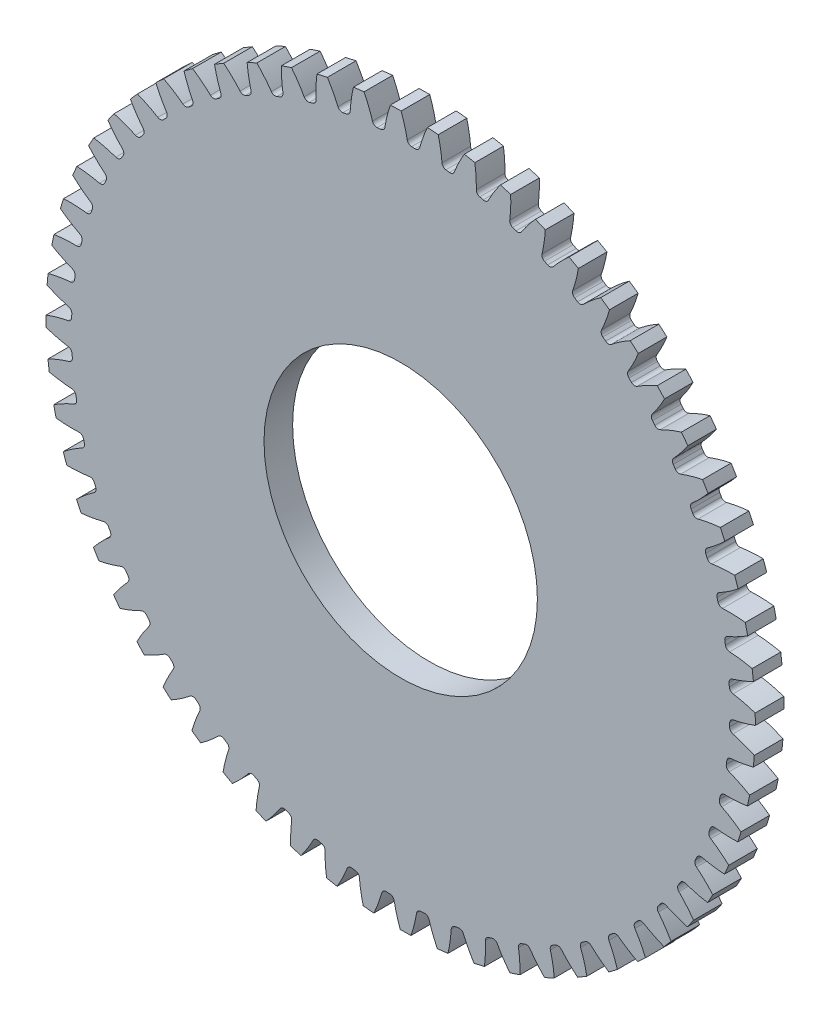
SolidWorks part; units mm, degrees
ref_plane "Front" through (0, 0, 0) normal (0, 0, 1) x (1, 0, 0)
ref_plane "Top" through (0, 0, 0) normal (0, 1, 0) x (1, 0, 0)
ref_plane "Right" through (0, 0, 0) normal (1, 0, 0) x (0, 0, -1)
sketch "Sketch3" plane through (0, 0, 0) normal (0, 0, 1) x (1, 0, 0)
  circle A0 centre (0, 0) radius 78.74
  dimension "od" = 157.48
extrude "gearBody" add sketch "Sketch3" along normal blind 6.35
sketch "Sketch2" plane through (0, 0, 0) normal (0, 0, 1) x (1, 0, 0)
  line L0 (0, 0) -> (68.1572, 28.2316) construction
  line L1 (92.002, -18.3096) -> (0, 0) construction
  line L2 (0, 0) -> (36.3143, 0) construction
  line L3 (76.1945, -0.916) -> (76.0401, -4.9343) construction
  line L5 (76.1173, -2.9252) -> (0, 0) construction
  line L7 (0, 0) -> (73.7729, 0) construction
  arc A0 (73.758, -1.4806) -> (73.6541, -4.1844) centre (0, 0) ccw construction
  arc A1 (78.7399, -0.0913) -> (78.5147, -5.9519) centre (0, 0) ccw construction
  arc A2 (76.1945, -0.916) -> (76.0401, -4.9343) centre (0, 0) ccw construction
  arc A3 (73.031, -3.2028) -> (73.0614, -2.4115) centre (0, 0) ccw
  arc A4 (92.002, -18.3096) -> (73.7695, -4.2158) centre (65.7895, -33.3792) ccw
  arc A5 (92.002, -18.3096) -> (93.1358, 11.1948) centre (0, 0) ccw
  arc A6 (93.1358, 11.1948) -> (73.8754, -1.4582) centre (68.1572, 28.2316) cw
  arc A7 (73.0614, -2.4115) -> (73.8754, -1.4582) centre (74.0654, -2.4446) cw
  arc A8 (73.7695, -4.2158) -> (73.031, -3.2028) centre (74.0346, -3.2468) cw
  point P6 (93.1358, 11.1948)
  point P22 (92.002, -18.3096)
  dimension "baseDia" = 147.5457
  dimension "od" = 157.48
  dimension "pd" = 152.4
  dimension "rd" = 146.2024
  dimension "rFillet" = 1.0046
  dimension "pointX" = 93.1358
  dimension "pointY" = 11.1948
  dimension "CTT" = 4.0183
  dimension "flankCenterAngle" = 22.5
extrude "toothCut" cut sketch "Sketch2" along normal through all
pattern_circular "CirPattern1" count 60 over 360 about axis through (0, 0, 6.35) along (0, 0, -1) of "toothCut"
ref_axis "toothSpace" through (0, 0, 0) along (0.9993, -0.0384, 0)
ref_axis "Axis2" through (78.4158, -7.1375, 0) along (-0.9959, 0.0906, 0)
sketch "hub1Dia" plane through (0, 0, 0) normal (0, 0, -1) x (-1, 0, 0)
  circle A0 centre (0, 0) radius 12.7
  dimension "hub1Dia" = 25.4
sketch "hub2Dia" plane through (0, 0, 6.35) normal (0, 0, 1) x (1, 0, 0)
  circle A0 centre (0, 0) radius 12.7
  dimension "hub2dia" = 25.4
sketch "boreDia" plane through (0, 0, 0) normal (0, 0, 1) x (1, 0, 0)
  circle A0 centre (0, 0) radius 30.353
  dimension "boreDia" = 60.706
extrude "bore" cut sketch "boreDia" against normal mid plane 25400
sketch "kwy1sketch" plane through (0, 0, 0) normal (0, 0, 1) x (1, 0, 0)
  line L0 (-5.3333, 0.3917) -> (0, 0) construction
  line L1 (56.5335, 8.5819) -> (54.6729, -16.7499)
  line L2 (54.6729, -16.7499) -> (23.0082, -14.4241)
  line L3 (56.5335, 8.5819) -> (24.8688, 10.9076)
  line L4 (23.0082, -14.4241) -> (0, 0)
  line L5 (0, 0) -> (24.8688, 10.9076)
  line L6 (0, 0) -> (73.0473, -2.8072) construction
  line L7 (55.6032, -4.084) -> (0, 0) construction
  arc A7 (73.031, -3.2028) -> (73.0614, -2.4115) centre (0, 0) ccw construction
  point P9 (55.6032, -4.084)
  point P13 (-0.8897, 0.0653)
  dimension "kwy1width" = 25.4
  dimension "kwy1depth" = 55.753
  dimension "kwy1angle" = 2
  dimension "kwy1Depth2" = 31.75
sketch "kwy2sketch" plane through (0, 0, 0) normal (0, 0, 1) x (1, 0, 0)
  line L0 (73.0473, -2.8072) -> (0, 0) construction
  line L1 (0, 0) -> (-2.7975, -2.4146) construction
  line L2 (33.9069, 46.0435) -> (50.5036, 26.8156)
  line L3 (50.5036, 26.8156) -> (26.4687, 6.0699)
  line L4 (33.9069, 46.0435) -> (9.8721, 25.2978)
  line L5 (26.4687, 6.0699) -> (0, 0)
  line L6 (0, 0) -> (9.8721, 25.2978)
  arc A2 (73.031, -3.2028) -> (73.0614, -2.4115) centre (0, 0) ccw construction
  point P10 (42.2052, 36.4296)
  dimension "kwy2angle" = 43
  dimension "kwy2Width" = 25.4
  dimension "kwy2depth" = 55.753
  dimension "kwy2Depth2" = 31.75
sketch "kwy3sketch" plane through (0, 0, 0) normal (0, 0, 1) x (1, 0, 0)
  line L0 (73.0473, -2.8072) -> (0, 0) construction
  line L1 (0, 0) -> (-0.1958, -2.6663) construction
  line L2 (-8.5819, 56.5335) -> (16.7499, 54.6729)
  line L3 (16.7499, 54.6729) -> (14.4241, 23.0082)
  line L4 (-8.5819, 56.5335) -> (-10.9076, 24.8688)
  line L5 (14.4241, 23.0082) -> (0, 0)
  line L6 (-10.9076, 24.8688) -> (0, 0)
  point P10 (4.084, 55.6032)
  dimension "kwy3angle" = 88
  dimension "kwy3depth" = 55.753
  dimension "kwy3width" = 25.4
  dimension "kwy3Depth2" = 31.75
sketch "kwy4sketch" plane through (0, 0, 0) normal (0, 0, 1) x (1, 0, 0)
  line L0 (73.0473, -2.8072) -> (0, 0) construction
  line L1 (0, 0) -> (1.3659, -1.5824) construction
  line L2 (-26.8156, 50.5036) -> (-46.0435, 33.9069)
  line L3 (-46.0435, 33.9069) -> (-25.2978, 9.8721)
  line L4 (-25.2978, 9.8721) -> (0, 0)
  line L5 (-6.0699, 26.4687) -> (0, 0)
  line L6 (-26.8156, 50.5036) -> (-6.0699, 26.4687)
  point P15 (-36.4296, 42.2052)
  dimension "kwy4angle" = 133
  dimension "kwy4depth" = 55.753
  dimension "kwy4width" = 25.4
  dimension "kwy4Depth2" = 31.75
sketch "kwy5sketch" plane through (0, 0, 0) normal (0, 0, 1) x (1, 0, 0)
  line L0 (73.0473, -2.8072) -> (0, 0) construction
  line L1 (0, 0) -> (1.7905, -0.1315) construction
  line L2 (-54.6729, 16.7499) -> (-56.5335, -8.5819)
  line L3 (-56.5335, -8.5819) -> (-24.8688, -10.9076)
  line L4 (-54.6729, 16.7499) -> (-23.0082, 14.4241)
  line L5 (-24.8688, -10.9076) -> (0, 0)
  line L6 (-23.0082, 14.4241) -> (0, 0)
  point P10 (-55.6032, 4.084)
  dimension "kwy5width" = 25.4
  dimension "kwy5depth" = 55.753
  dimension "kwy5angle" = 178
  dimension "kwy5Depth2" = 31.75
sketch "kwy6sketch" plane through (0, 0, 0) normal (0, 0, 1) x (1, 0, 0)
  line L0 (73.0473, -2.8072) -> (0, 0) construction
  line L1 (0, 0) -> (1.358, 1.1721) construction
  line L2 (-50.5036, -26.8156) -> (-33.9069, -46.0435)
  line L3 (-33.9069, -46.0435) -> (-9.8721, -25.2978)
  line L4 (-50.5036, -26.8156) -> (-26.4687, -6.0699)
  line L5 (-9.8721, -25.2978) -> (0, 0)
  line L6 (-26.4687, -6.0699) -> (0, 0)
  point P10 (-42.2052, -36.4296)
  dimension "kwy6angle" = 223
  dimension "kwy6width" = 25.4
  dimension "kwy6depth" = 55.753
  dimension "kwy6Depth2" = 31.75
sketch "kwy7sketch" plane through (0, 0, 0) normal (0, 0, 1) x (1, 0, 0)
  line L0 (73.0473, -2.8072) -> (0, 0) construction
  line L1 (0, 0) -> (0.1472, 2.0043) construction
  line L2 (-16.7499, -54.6729) -> (8.5819, -56.5335)
  line L3 (-16.7499, -54.6729) -> (-14.4241, -23.0082)
  line L4 (8.5819, -56.5335) -> (10.9076, -24.8688)
  line L5 (-14.4241, -23.0082) -> (0, 0)
  line L6 (10.9076, -24.8688) -> (0, 0)
  point P10 (-4.084, -55.6032)
  dimension "kwy7angle" = 88
  dimension "kwy7width" = 25.4
  dimension "kwy7depth" = 55.753
  dimension "kwy7angle1" = 268
  dimension "kwy7Depth2" = 31.75
sketch "kwy8sketch" plane through (0, 0, 0) normal (0, 0, 1) x (1, 0, 0)
  line L0 (73.0473, -2.8072) -> (0, 0) construction
  line L1 (0, 0) -> (-1.1667, 1.3516) construction
  line L2 (26.8156, -50.5036) -> (46.0435, -33.9069)
  line L3 (46.0435, -33.9069) -> (25.2978, -9.8721)
  line L4 (26.8156, -50.5036) -> (6.0699, -26.4687)
  line L5 (25.2978, -9.8721) -> (0, 0)
  line L6 (6.0699, -26.4687) -> (0, 0)
  point P10 (36.4296, -42.2052)
  dimension "kwy8angle" = 313
  dimension "kwy8width" = 25.4
  dimension "kwy8depth" = 55.753
  dimension "kwy8Depth2" = 31.75
sketch "centerLine" plane through (0, 0, 0) normal (0, 1, 0) x (1, 0, 0)
  line L0 (0, 36.4807) -> (0, -59.6309) construction
ref_plane "CB1plane" through (0, 0, 0) normal (0, 0, -1) x (-1, 0, 0)
sketch "CB1diameter" plane through (0, 0, 0) normal (0, 0, -1) x (-1, 0, 0)
  circle A0 centre (0, 0) radius 12.7
  dimension "CB1diameter" = 25.4
ref_plane "CB2plane" through (0, 0, 6.35) normal (0, 0, 1) x (1, 0, 0)
sketch "CB2diameter" plane through (0, 0, 6.35) normal (0, 0, 1) x (1, 0, 0)
  circle A0 centre (0, 0) radius 12.7
  dimension "CB2diameter" = 25.4
ref_axis "Axis1" through (0, 0, 50) along (0, 0, -1)
sketch3d "3DSketch1" plane through (0, 0, 0) normal (0, 0, 1) x (1, 0, 0)
